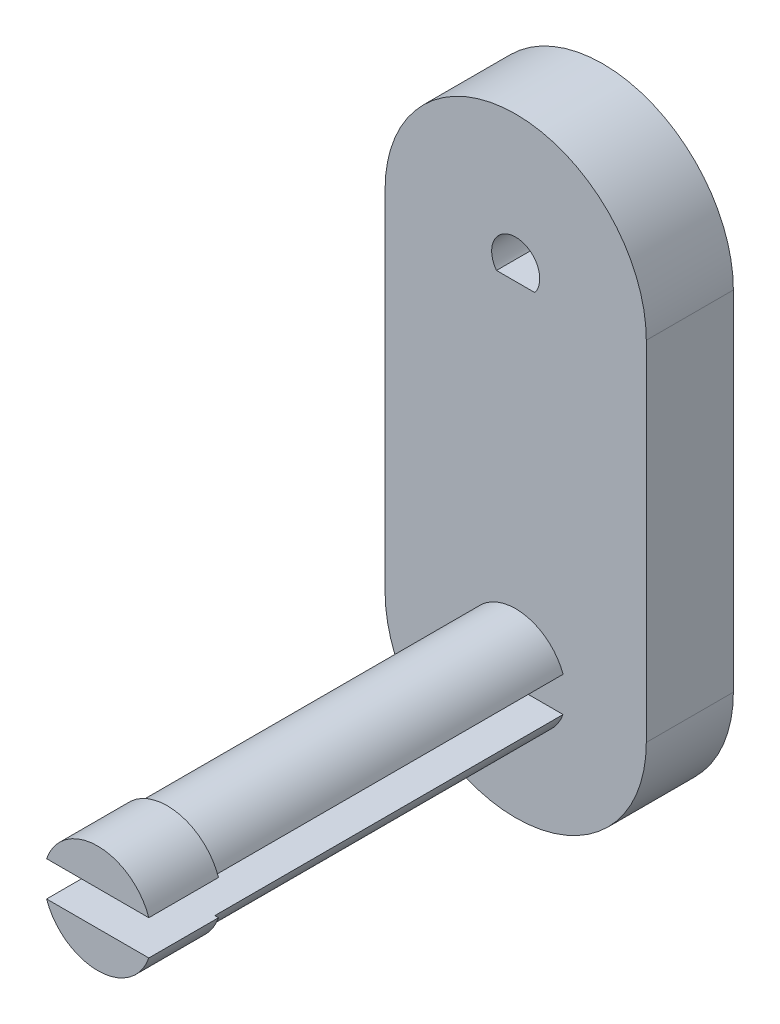
SolidWorks part; units mm, degrees
ref_plane "Plan de face" through (0, 0, 0) normal (0, 0, 1) x (1, 0, 0)
ref_plane "Plan de dessus" through (0, 0, 0) normal (0, 1, 0) x (1, 0, 0)
ref_plane "Plan de droite" through (0, 0, 0) normal (1, 0, 0) x (0, 0, -1)
sketch "Esquisse1" plane through (0, 0, 0) normal (0, 0, -1) x (-1, 0, 0)
  line L0 (0, 0) -> (0, -20) construction
  line L1 (7.5, 0) -> (7.5, -20)
  line L2 (-7.5, 0) -> (-7.5, -20)
  arc A0 (7.5, 0) -> (-7.5, 0) centre (0, 0) ccw
  arc A1 (-7.5, -20) -> (7.5, -20) centre (0, -20) ccw
  point P4 (0, -10)
  dimension "D1" = 15
extrude "Boss.-Extru.1" add sketch "Esquisse1" along normal blind 5 from offset 10
sketch "Esquisse2" plane through (0, 0, -10) normal (0, 0, 1) x (1, 0, 0)
  circle A0 centre (0, -20) radius 2.9
  dimension "D1" = 5.8
extrude "Boss.-Extru.2" add sketch "Esquisse2" along normal blind 20
sketch "Esquisse3" plane through (0, 0, 10) normal (0, 0, 1) x (1, 0, 0)
  circle A0 centre (0, -20) radius 3.1
  dimension "D1" = 6.2
extrude "Boss.-Extru.3" add sketch "Esquisse3" along normal blind 4
sketch "Esquisse4" plane through (0, 0, 14) normal (0, 0, 1) x (1, 0, 0)
  line L1 (-5, -19) -> (5, -19)
  line L2 (-5, -19) -> (-5, -21)
  line L3 (-5, -21) -> (5, -21)
  line L4 (5, -19) -> (5, -21)
  point P4 (0, -21)
  dimension "D1" = 1
  dimension "D2" = 1
  dimension "D3" = 10
  dimension "D4" = 5
extrude "Enlèv. mat.-Extru.1" cut sketch "Esquisse4" against normal blind 24
sketch "Esquisse5" plane through (0, 0, -10) normal (0, 0, 1) x (1, 0, 0)
  line L0 (0, -0.83) -> (-1.1025, -0.83)
  line L1 (-1.1025, -0.83) -> (1.1025, -0.83)
  circle A0 centre (0, 0) radius 0.83
  circle A1 centre (0, 0) radius 1.38
  arc A2 (-1.1025, -0.83) -> (1.1025, -0.83) centre (0, 0) cw
  dimension "D1" = 1.66
extrude "Enlèv. mat.-Extru.2" cut sketch "Esquisse5" against normal blind 24 contours A0 | L1 A1 L0 A0 region at (-0.5512, -0.7946, -10) region at (0, 0, -10)
